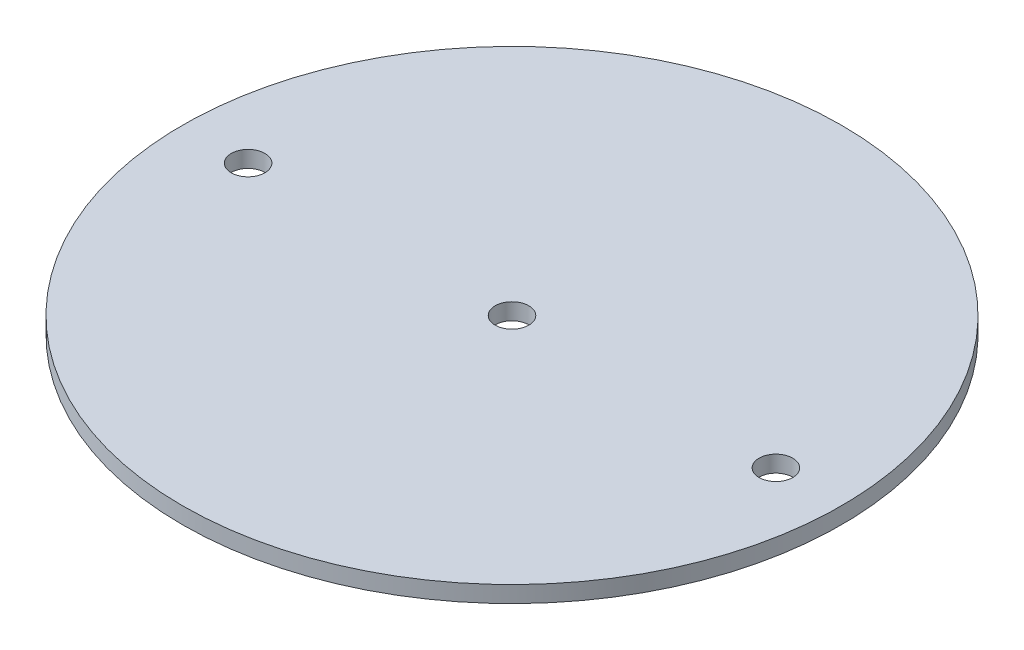
SolidWorks part; units mm, degrees
ref_plane "Front Plane" through (0, 0, 0) normal (0, 0, 1) x (1, 0, 0)
ref_plane "Top Plane" through (0, 0, 0) normal (0, 1, 0) x (1, 0, 0)
ref_plane "Right Plane" through (0, 0, 0) normal (1, 0, 0) x (0, 0, -1)
sketch "Sketch2" plane through (0, 0, 0) normal (0, 1, 0) x (1, 0, 0)
  line L0 (-50.8, 0) -> (50.8, 0) construction
  circle A0 centre (0, 0) radius 63.4365
  circle A1 centre (-50.8, 0) radius 3.2385
  circle A2 centre (50.8, 0) radius 3.2385
  circle A3 centre (0, 0) radius 3.2385
  point P6 (0, 0)
  dimension "D1" = 126.873
  dimension "D3" = 6.477
  dimension "D4" = 6.477
  dimension "D2" = 101.6
extrude "Boss-Extrude1" add sketch "Sketch2" along normal blind 3.175
